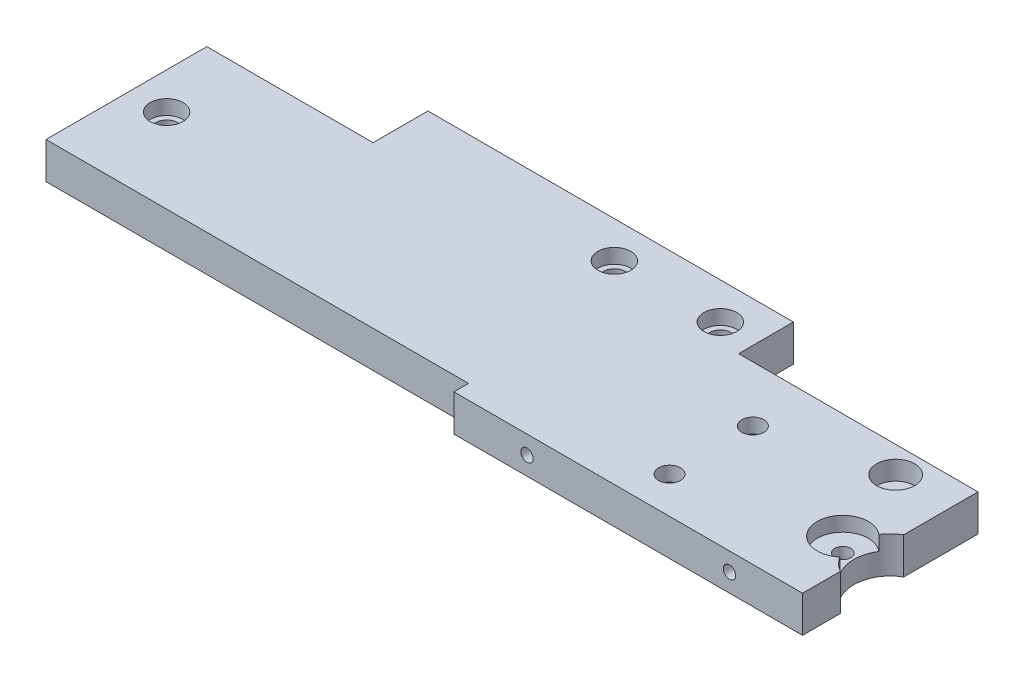
SolidWorks part; units mm, degrees
other "标注1"
sketch "草图3" plane through (0, 5, 29.5) normal (-0.6417, 0.7662, 0.0339) x (0.7661, 0.6384, 0.0747)
ref_plane "前视基准面" through (0, 0, 0) normal (0, 0, 1) x (1, 0, 0)
ref_plane "上视基准面" through (0, 0, 0) normal (0, 1, 0) x (1, 0, 0)
ref_plane "右视基准面" through (0, 0, 0) normal (1, 0, 0) x (0, 0, -1)
other "Configuration Table"
sketch "草图1" plane through (0, 0, 0) normal (0, 1, 0) x (1, 0, 0)
  line L0 (19.7074, -14.6) -> (48.9981, -14.6) construction
  line L33 (-50, -29.5) -> (0, -29.5)
  line L34 (-50, -29.5) -> (-50, 0)
  line L36 (0, -29.5) -> (0, 0)
  line L37 (-50, 0) -> (0, 0)
  line L38 (-72.75, -7.5) -> (32.75, -7.5)
  line L39 (-72.75, -7.5) -> (-72.75, -29.5)
  line L40 (-72.75, -29.5) -> (32.75, -29.5)
  line L41 (32.75, -7.5) -> (32.75, -29.5)
  line L48 (49.4474, -17.6) -> (56.141, -17.6) construction
  circle A7 centre (28.75, -22) radius 1.1
  circle A8 centre (25.0839, -11.1) radius 1.1
  circle A10 centre (25.0839, -11.1) radius 2.6
  circle A11 centre (35.25, -22) radius 5
  circle A13 centre (-19.5, -5) radius 2.25
  circle A14 centre (-19.5, -5) radius 1.5
  circle A15 centre (-5, -5) radius 1.5
  circle A16 centre (-5, -5) radius 2.25
  circle A18 centre (-67.75, -18) radius 1.5
  circle A19 centre (-67.75, -18) radius 2.25
  circle A20 centre (28.75, -22) radius 3.5
  point P0 (-90.6464, 22.0667)
  dimension "D1" = 2.2
  dimension "D2" = 29.5
  dimension "D3" = 11.5
  dimension "D4" = 50
  dimension "D5" = 6.5
  dimension "D9" = 3
  dimension "D10" = 4.5
  dimension "D13" = 6.5
  dimension "D15" = 10
  dimension "D6" = 5.2
  dimension "D17" = 7
  dimension "D7" = 4
  dimension "D8" = 2.5
  dimension "D11" = 14.5
  dimension "D12" = 5
  dimension "D14" = 5
  dimension "D16" = 5
extrude "凸台-拉伸1" add sketch "草图1" along normal blind 5 contours L34 | L37 L36 L33 L34 | L38 L41 L40 L39 region at (-61.1658, 0, 18.5164)
extrude "切除-拉伸2" cut sketch "草图1<20>" along normal through all contours A14 | A15 | A18
sketch "草图1<20>" plane through (0, 0, 0) normal (0, 1, 0) x (1, 0, 0) same geometry as "草图1"
extrude "切除-拉伸3" cut sketch "草图1<22>" against normal blind 2 from surface contours A13 | A16 | A19 starting at face at (-67.75, 5, 19.5)
sketch "草图1<22>" plane through (0, 0, 0) normal (0, 1, 0) x (1, 0, 0) same geometry as "草图1"
extrude "切除-拉伸4" cut sketch "草图1<23>" against normal blind 2.6 from surface contours A10 starting at face at (-67.75, 5, 20.25)
sketch "草图1<23>" plane through (0, 0, 0) normal (0, 1, 0) x (1, 0, 0) same geometry as "草图1"
extrude "切除-拉伸6" cut sketch "草图1<24>" against normal through all from surface contours A8 | A7 starting at face at (25.0839, 5, 13.7)
sketch "草图1<24>" plane through (0, 0, 0) normal (0, 1, 0) x (1, 0, 0) same geometry as "草图1"
sketch "草图4" plane through (0, 0, 0) normal (0, -1, 0) x (1, 0, 0)
  circle A0 centre (9.548, 15.1) radius 2.25
  circle A1 centre (9.548, 26.5) radius 2.25
  circle A2 centre (9.548, 15.1) radius 1.5
  circle A3 centre (9.548, 26.5) radius 1.5
  point P6 (0, 0)
  point P7 (0, 0)
  dimension "D1" = 3
  dimension "D2" = 4.5
extrude "切除-拉伸7" cut sketch "草图4" against normal through all contours A2 | A3
extrude "切除-拉伸8" cut sketch "草图4<3>" against normal offset from surface (3 mm away) 2 contours A1 | A0 up to face at (9.548, 5, 13.6)
sketch "草图4<3>" plane through (0, 0, 0) normal (0, -1, 0) x (1, 0, 0) same geometry as "草图4"
sketch "草图5" plane through (0, 0, 29.5) normal (0, 0, 1) x (1, 0, 0)
  line L1 (32.75, 5) -> (-14.952, 5)
  line L2 (32.75, 5) -> (32.75, 0)
  line L3 (32.75, 0) -> (-14.952, 0)
  line L4 (-14.952, 5) -> (-14.952, 0)
  dimension "D1" = 47.702
extrude "凸台-拉伸2" add sketch "草图5" along normal blind 2
sketch "草图6" plane through (0, 0, 31.5) normal (0, 0, 1) x (1, 0, 0)
  line L0 (32.75, 0) -> (32.75, 5) construction
  line L1 (-14.952, 5) -> (-14.952, 0) construction
  circle A0 centre (22.75, 2.5) radius 0.85
  circle A1 centre (-4.952, 2.5) radius 0.85
  point P4 (0, 0)
  point P7 (0, 0)
  point P10 (0, 0)
  point P11 (32.75, 2.5)
  dimension "D1" = 1.7
  dimension "D2" = 10
  dimension "D3" = 10
extrude "切除-拉伸9" cut sketch "草图6" against normal blind 4 contours A1 | A0
extrude "切除-拉伸12" cut sketch "草图1<25>" along normal through all contours A11
sketch "草图1<25>" plane through (0, 0, 0) normal (0, 1, 0) x (1, 0, 0) same geometry as "草图1"
extrude "切除-拉伸13" cut sketch "草图1<26>" against normal blind 2 from surface contours A20 starting at face at (9.548, 5, 13.6)
sketch "草图1<26>" plane through (0, 0, 0) normal (0, 1, 0) x (1, 0, 0) same geometry as "草图1"
